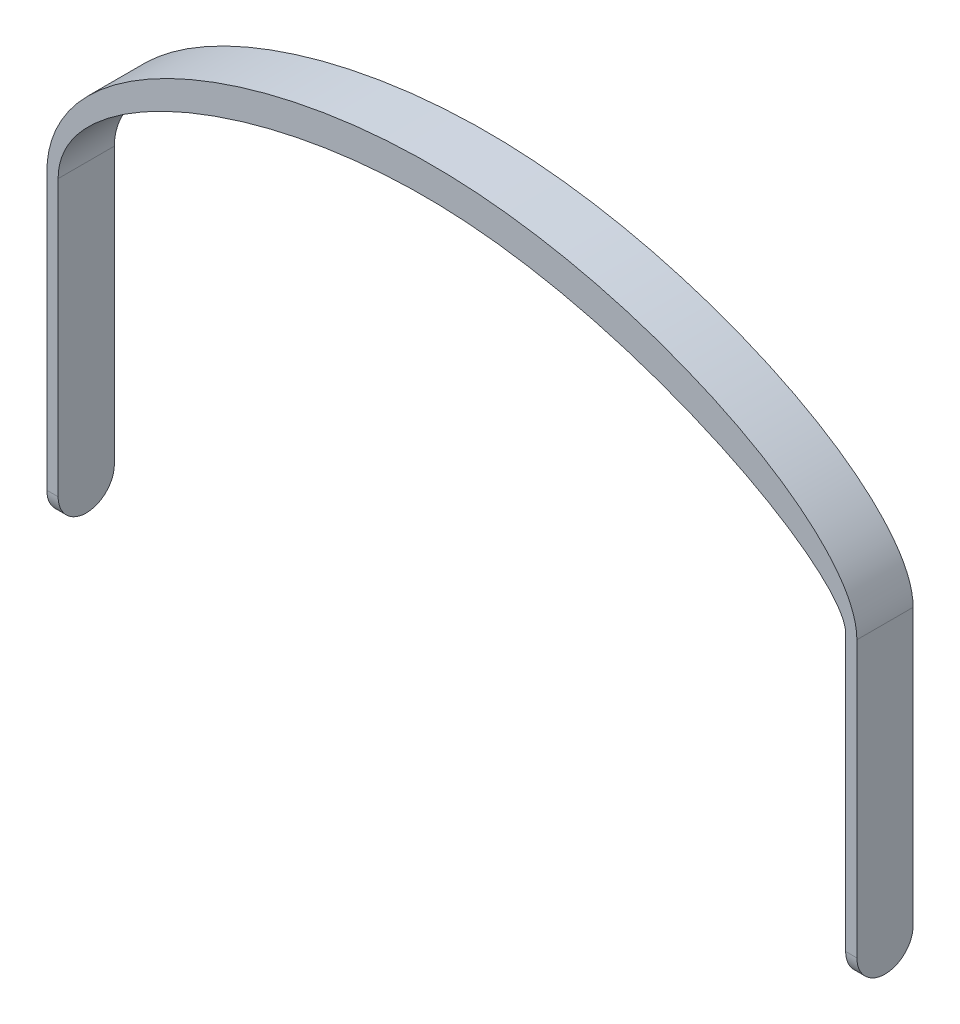
SolidWorks part; units mm, degrees
ref_plane "Front Plane" through (0, 0, 0) normal (0, 0, 1) x (1, 0, 0)
ref_plane "Top Plane" through (0, 0, 0) normal (0, 1, 0) x (1, 0, 0)
ref_plane "Right Plane" through (0, 0, 0) normal (1, 0, 0) x (0, 0, -1)
sketch "Sketch3" plane through (0, 0, 0) normal (0, 0, 1) x (1, 0, 0)
  line L0 (-177.8, 7.5786) -> (-177.8, -129.54)
  line L1 (-177.8, -129.54) -> (-182.88, -129.54)
  line L2 (-182.88, -129.54) -> (-182.88, 7.5786)
  line L3 (0, 0) -> (0, -90.4284) construction
  line L4 (182.88, -129.54) -> (182.88, 7.5786)
  line L5 (177.8, 7.5786) -> (177.8, -129.54)
  line L6 (177.8, -129.54) -> (182.88, -129.54)
  spline S0 degree 3 poles (-177.8, 7.5786) (-177.8, 46.3001) (0, 128.0422) (177.8, 30.0171) (177.8, 7.5786) knots 0 0 0 0 0.5 1 1 1 1
  spline S1 degree 3 poles (182.88, 7.5786) (182.88, 46.7638) (0, 141.3945) (-182.88, 58.9081) (-182.88, 7.5786) knots 0 0 0 0 0.5 1 1 1 1
  dimension "D1" = 177.8
  dimension "D2" = 5.08
  dimension "D3" = 129.54
extrude "Boss-Extrude2" add sketch "Sketch3" along normal blind 25.4 contours L4 S1 L2 L1 L0 S0 L5 L6
fillet "Fillet1" radius 12.7 2 edges at (-180.34, -129.54, 0) (-180.34, -129.54, 25.4)
fillet "Fillet2" radius 12.7 2 edges at (180.34, -129.54, 0) (180.34, -129.54, 25.4)
ref_axis "Axis1" through (0, 83.1004, 25.4) along (0, 0, -1)
